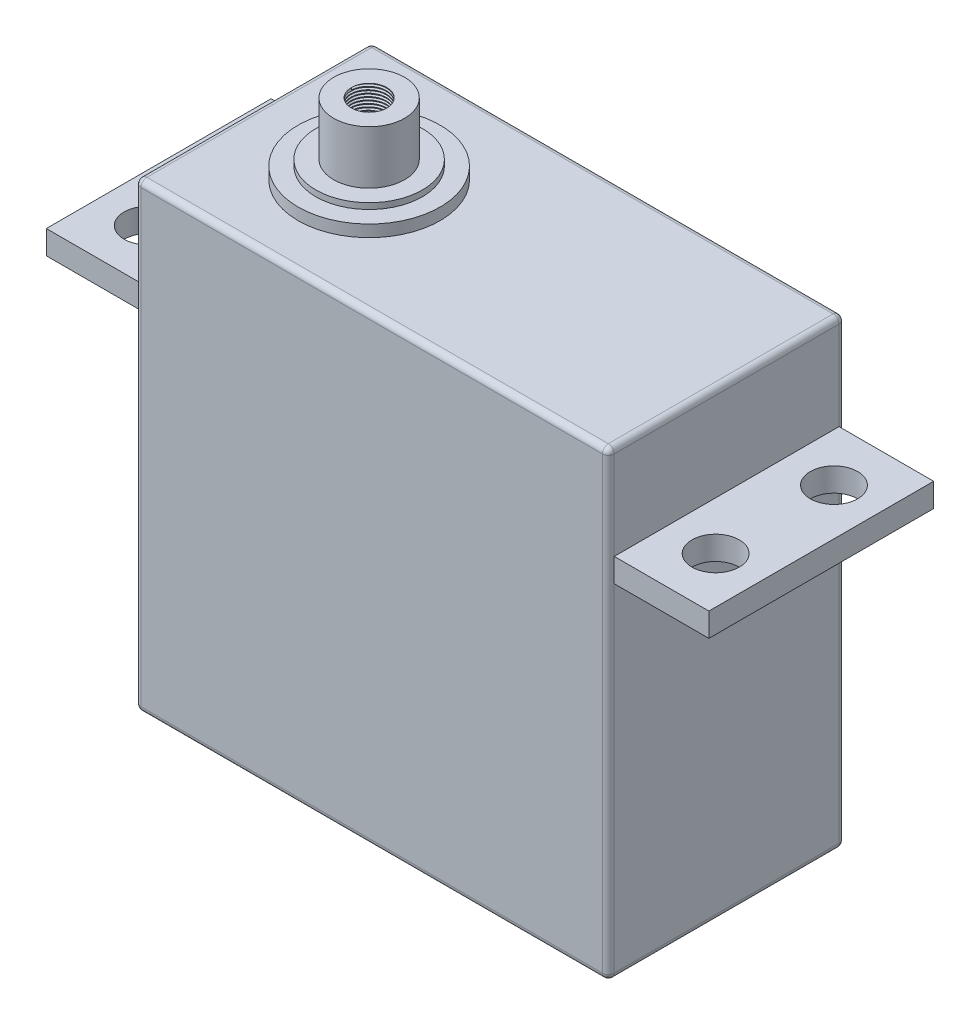
SolidWorks part; units mm, degrees
ref_plane "前视基准面" through (0, 0, 0) normal (0, 0, 1) x (1, 0, 0)
ref_plane "上视基准面" through (0, 0, 0) normal (0, 1, 0) x (1, 0, 0)
ref_plane "右视基准面" through (0, 0, 0) normal (1, 0, 0) x (0, 0, -1)
other "Configuration Table"
sketch "草图1" plane through (0, 0, 0) normal (0, 0, 1) x (1, 0, 0)
  line L1 (0, 0) -> (40, 0)
  line L2 (0, 0) -> (0, 39)
  line L3 (0, 39) -> (40, 39)
  line L4 (40, 0) -> (40, 39)
  dimension "D1" = 40
  dimension "D2" = 39
extrude "凸台-拉伸2" add sketch "草图1" along normal blind 20 contours L3 L4 L1 L2
fillet "圆角2" radius 0.5 2 edges at (40, 19.5, 20) (20, 39, 20)
fillet "圆角3" radius 0.5 6 edges at (40, 0, 9.75) (39.8536, 0, 19.8536) (0, 39, 9.75) (0, 38.8536, 19.8536) (19.75, 0, 20) (0, 19.25, 20)
fillet "圆角4" radius 0.5 5 edges at (39.8536, 38.8536, 19.8536) (19.75, 0, 0) (39.8536, 0.1464, 0) (40, 39, 9.75) (40, 19.75, 0)
fillet "圆角5" radius 0.5 7 edges at (0.1464, 0.1464, 19.8536) (0, 0, 10) (0, 0.1464, 0.1464) (39.8536, 38.8536, 0.1464) (20, 39, 0) (0.1464, 38.8536, 0) (0, 19.5, 0)
sketch "草图6" plane through (0, 0, 0) normal (-1, 0, 0) x (0, 0, 1)
  line L0 (19.5, 0.5) -> (19.5, 38.5) construction
  line L1 (0.5, 38.5) -> (0.5, 0.5) construction
  line L2 (19.5, 31) -> (0.5, 31)
  line L3 (19.5, 31) -> (19.5, 29)
  line L4 (19.5, 29) -> (0.5, 29)
  line L5 (0.5, 31) -> (0.5, 29)
  line L6 (19.5, 0) -> (0.5, 0) construction
  dimension "D1" = 2
  dimension "D2" = 31
extrude "凸台-拉伸3" add sketch "草图6" along normal blind 8
sketch "草图7" plane through (40, 0, 0) normal (1, 0, 0) x (0, 0, -1)
  line L0 (-0.5, 0.5) -> (-0.5, 38.5) construction
  line L1 (-0.5, 31) -> (-19.5, 31)
  line L2 (-0.5, 31) -> (-0.5, 29)
  line L3 (-0.5, 29) -> (-19.5, 29)
  line L4 (-19.5, 31) -> (-19.5, 29)
  line L5 (-19.5, 38.5) -> (-19.5, 0.5) construction
  line L6 (-0.5, 0) -> (-19.5, 0) construction
  dimension "D1" = 2
  dimension "D2" = 31
extrude "凸台-拉伸5" add sketch "草图7" along normal blind 8
sketch "草图8" plane through (0, 39, 0) normal (0, 1, 0) x (1, 0, 0)
  line L1 (-8, -10) -> (48, -10) construction
  line L2 (-8, -19.5) -> (-8, -0.5) construction
  line L3 (48, -0.5) -> (48, -19.5) construction
  circle A0 centre (-3.9282, -5) radius 2
  circle A1 centre (-3.9282, -15) radius 2
  circle A2 centre (44.0718, -5) radius 2
  circle A3 centre (44.0718, -15) radius 2
  dimension "D1" = 4
  dimension "D2" = 4
  dimension "D3" = 4
  dimension "D4" = 4
  dimension "D5" = 10
  dimension "D6" = 10
  dimension "D7" = 48
extrude "切除-拉伸1" cut sketch "草图8" against normal blind 28
sketch "草图9" plane through (0, 39, 0) normal (0, 1, 0) x (1, 0, 0)
  circle A0 centre (10.0718, -10.288) radius 6
  circle A1 centre (10.0718, -10.288) radius 4.5
  circle A2 centre (10.0718, -10.288) radius 3
  point P4 (-3.9282, -5)
  dimension "D1" = 12
  dimension "D2" = 9
  dimension "D3" = 6
  dimension "D4" = 14
extrude "凸台-拉伸7" add sketch "草图9" along normal blind 1 contours A0 A1 region at (4.2416, 39, 10.288)
sketch "草图10" plane through (0, 39, 0) normal (0, 1, 0) x (1, 0, 0)
  circle A0 centre (10.0718, -10.288) radius 4.5
extrude "凸台-拉伸8" add sketch "草图10" along normal blind 1.5
sketch "草图11" plane through (0, 40.5, 0) normal (0, 1, 0) x (1, 0, 0)
  circle A0 centre (10.0718, -10.288) radius 3
  dimension "D1" = 6
extrude "凸台-拉伸9" add sketch "草图11" along normal blind 4.5
sketch "草图12" plane through (0, 45, 0) normal (0, 1, 0) x (1, 0, 0)
  circle A0 centre (10.0718, -10.288) radius 1.5
  dimension "D1" = 3
extrude "切除-拉伸2" cut sketch "草图12" against normal blind 6
thread "螺纹线1" pitch 0.25 method cut profile "螺纹线轮廓2" start angle 0, offset 0, length 6, pitch 0.25, diameter 3
ref_plane "基准面2" through (8.5718, 45, 10.288) normal (0, 0, 1) x (-1, 0, 0)
sketch "螺纹线轮廓2" plane through (8.5718, 45, 10.288) normal (0, 0, 1) x (-1, 0, 0)
  line L0 (0, 0) -> (0, 0.25) construction
  line L1 (0, 0) -> (0.1353, 0.0781)
  line L2 (0.1353, 0.0781) -> (0.1353, 0.1094)
  line L3 (0.1353, 0.1094) -> (0, 0.1875)
  line L4 (0.1353, 0.0937) -> (0, 0.0937) construction
  line L11 (0, 0) -> (0, 0.1875)
  point P2 (0, 0)
  dimension "Pitch" = 0.25
  dimension "Profile_Angle" = 60
  dimension "Profile_Land" = 0.0312
  dimension "Profile_Height" = 0.1353
